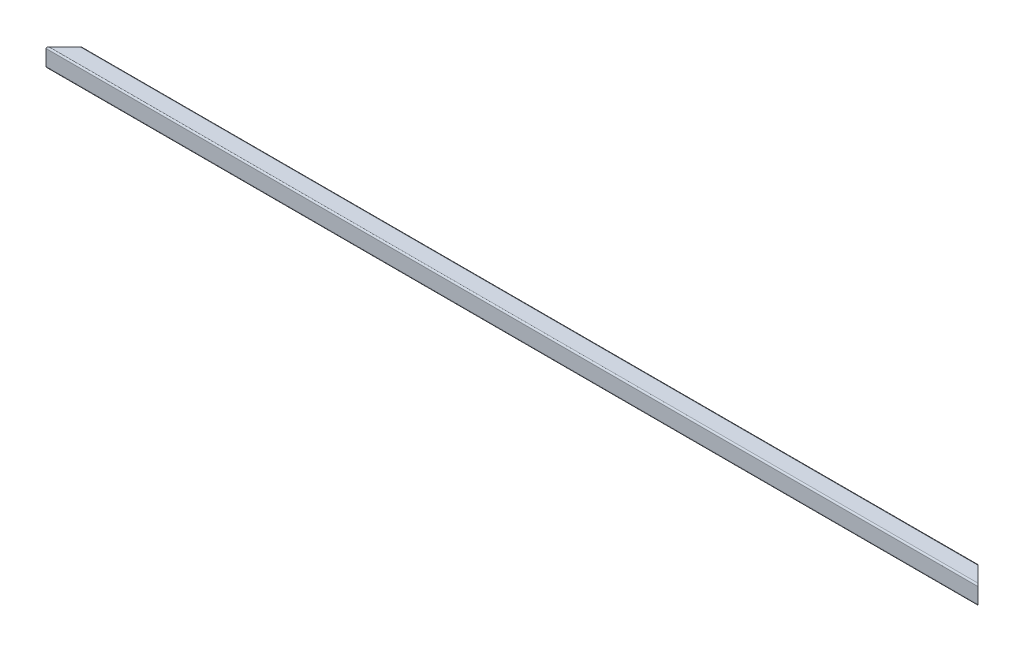
SolidWorks part; units mm, degrees
material "Plain Carbon Steel"
ref_plane "Front Plane" through (0, 0, 0) normal (0, 0, 1) x (1, 0, 0)
ref_plane "Top Plane" through (0, 0, 0) normal (0, 1, 0) x (1, 0, 0)
ref_plane "Right Plane" through (0, 0, 0) normal (1, 0, 0) x (0, 0, -1)
sketch "Sketch1" plane through (0, 0, 0) normal (1, 0, 0) x (0, 0, -1)
  line L0 (0, 2.54) -> (0, 29.21)
  line L1 (-2.54, 31.75) -> (-29.21, 31.75)
  line L2 (-31.75, 29.21) -> (-31.75, 2.54)
  line L3 (-29.21, 0) -> (-2.54, 0)
  line L4 (-4.1275, 4.1275) -> (-4.1275, 27.6225)
  line L5 (-4.1275, 27.6225) -> (-27.6225, 27.6225)
  line L6 (-27.6225, 27.6225) -> (-27.6225, 4.1275)
  line L7 (-27.6225, 4.1275) -> (-4.1275, 4.1275)
  arc A0 (-31.75, 2.54) -> (-29.21, 0) centre (-29.21, 2.54) ccw
  arc A1 (0, 2.54) -> (-2.54, 0) centre (-2.54, 2.54) cw
  arc A2 (0, 29.21) -> (-2.54, 31.75) centre (-2.54, 29.21) ccw
  arc A3 (-31.75, 29.21) -> (-29.21, 31.75) centre (-29.21, 29.21) cw
  arc A4 (-4.1275, 27.6225) -> (-4.1275, 27.6225) centre (-4.1275, 27.6225) ccw
  arc A5 (-27.6225, 27.6225) -> (-27.6225, 27.6225) centre (-27.6225, 27.6225) cw
  arc A6 (-27.6225, 4.1275) -> (-27.6225, 4.1275) centre (-27.6225, 4.1275) ccw
  arc A7 (-4.1275, 4.1275) -> (-4.1275, 4.1275) centre (-4.1275, 4.1275) cw
  point P12 (0, 0)
  point P15 (0, 31.75)
  point P18 (-31.75, 31.75)
  dimension "D3" = 2.54
  dimension "D1" = 31.75
  dimension "D2" = 31.75
  dimension "D4" = 4.1275
extrude "Boss-Extrude1" add sketch "Sketch1" along normal blind 641.7872
scale "Scale1" scale about centroid uniform scaling no x scale factor 1 y scale factor 0.4 z scale factor 0.4
sketch "Sketch2" plane through (0, 0, 22.225) normal (0, 0, -1) x (-1, 0, 0)
  line L0 (-641.7872, 9.525) -> (0, 9.525) construction
  point P4 (-320.8936, 9.525)
sketch "Sketch3" plane through (0, 22.225, 0) normal (0, 1, 0) x (1, 0, 0)
  line L0 (0, -22.225) -> (12.7, -22.225) construction
  line L7 (12.7, -22.225) -> (12.7, -9.525) construction
  line L8 (6.35, -22.225) -> (6.35, -9.525) construction
  line L12 (641.7872, -22.225) -> (0, -22.225) construction
  line L13 (320.8936, -10.541) -> (320.8936, -21.209) construction
  line L14 (641.7872, -10.541) -> (0, -10.541) construction
  line L15 (641.7872, -21.209) -> (0, -21.209) construction
  line L19 (0, -10.541) -> (0, -21.209) construction
  line L21 (0, -9.525) -> (0, -22.225)
  line L22 (0, -15.875) -> (6.35, -15.875) construction
  line L23 (641.7872, -10.541) -> (641.7872, -21.209) construction
  line L26 (0, -9.525) -> (0, -10.541) construction
  line L27 (6.35, -15.875) -> (12.7, -15.875) construction
  line L28 (0, -22.225) -> (12.7, -9.525)
  line L29 (12.7, -9.525) -> (0, -9.525)
  line L33 (641.7872, -9.525) -> (641.7872, -22.225)
  line L34 (641.7872, -9.525) -> (0, -9.525) construction
  line L35 (641.7872, -22.225) -> (629.0872, -9.525)
  line L36 (629.0872, -9.525) -> (641.7872, -9.525)
  point P5 (639.254, -9.525)
  point P6 (6.35, -15.875)
  point P7 (641.7872, -22.225)
  point P9 (12.7, -15.875)
  point P125 (6.35, -15.875)
  dimension "D1" = 12.7
  dimension "D2" = 12.7
  dimension "D3" = 12.7
extrude "Cut-Extrude1" cut sketch "Sketch3" against normal through all
